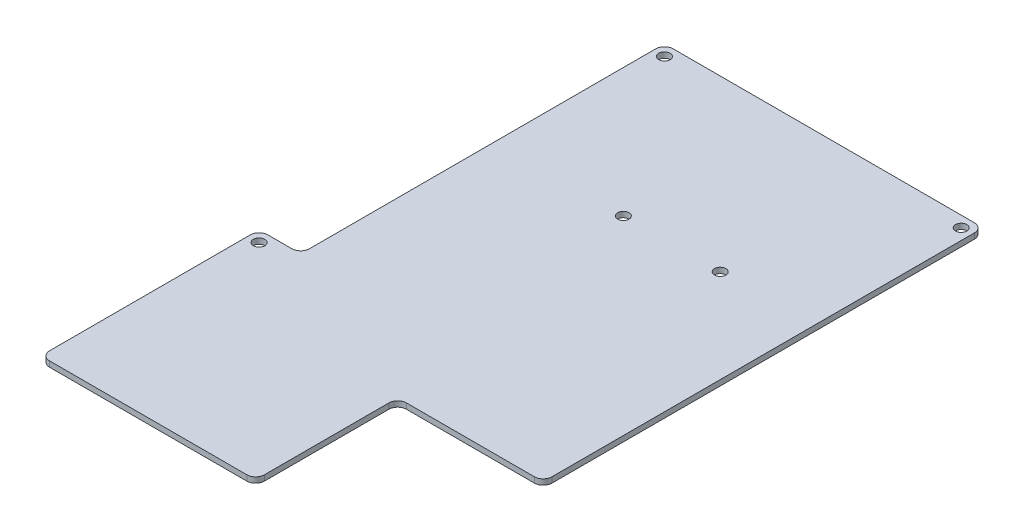
SolidWorks part; units mm, degrees
ref_plane "Front" through (0, 0, 0) normal (0, 0, 1) x (1, 0, 0)
ref_plane "Top" through (0, 0, 0) normal (0, 1, 0) x (1, 0, 0)
ref_plane "Right" through (0, 0, 0) normal (1, 0, 0) x (0, 0, -1)
sketch "Sketch1" plane through (0, 0, 0) normal (0, 1, 0) x (1, 0, 0)
  line L1 (-46, -63.5) -> (46, -63.5)
  line L2 (-46, -63.5) -> (-46, 63.5)
  line L3 (-46, 63.5) -> (46, 63.5)
  line L4 (46, -63.5) -> (46, 63.5)
  line L5 (-46, -63.5) -> (46, 63.5) construction
  line L6 (-46, 63.5) -> (46, -63.5) construction
  point P0 (0, 0)
  dimension "D1" = 127
  dimension "D2" = 92
extrude "Boss-Extrude1" add sketch "Sketch1" along normal blind 1.6
hole_wizard "#4 Clearance Hole1" positions "Sketch4" profile "Sketch5" hole size "#4" standard "ANSI Inch"
sketch "Sketch4" plane through (0, 1.6, 0) normal (0, 1, 0) x (1, 0, 0)
  line L1 (46, -63.5) -> (46, 63.5) construction
  line L2 (46, 63.5) -> (-46, 63.5) construction
  line L3 (-46, 63.5) -> (-46, -63.5) construction
  point P22 (19.05, 14.54)
  point P24 (-8.89, 14.54)
  dimension "D1" = 26.95
  dimension "D2" = 48.96
  dimension "D3" = 48.96
  dimension "D4" = 37.11
sketch "Sketch5" plane through (19.05, 1.6, -14.54) normal (1, 0, 0) x (0, 0, 1)
  line L0 (0, 0) -> (0, 19.7306)
  line L1 (0, 19.7306) -> (1.6319, 18.75)
  line L2 (1.6319, 18.75) -> (1.6319, 0)
  line L5 (1.6319, 0) -> (0, 0)
  line L10 (0, 19.7306) -> (-1.632, 18.75) construction
  line L11 (0, -6.35) -> (0, 107.95) construction
  dimension "Hole Dia." = 3.2639
  dimension "Hole Depth" = 18.75
  dimension "Drill Angle" = 118
hole_wizard "#8 Clearance Hole1" positions "Sketch6" profile "Sketch7" hole size "#8" standard "ANSI Inch"
sketch "Sketch6" plane through (0, 0, 0) normal (0, -1, 0) x (-1, 0, 0)
  circle A0 centre (22.07, -45.25) radius 1.5 construction
  point P0 (22.07, -45.25)
sketch "Sketch7" plane through (-22.07, 0, 45.25) normal (1, 0, 0) x (0, 0, -1)
  line L0 (0, 0) -> (0, 20.1007)
  line L1 (0, 20.1007) -> (2.2479, 18.75)
  line L2 (2.2479, 18.75) -> (2.2479, 0)
  line L5 (2.2479, 0) -> (0, 0)
  line L10 (0, 20.1007) -> (-2.2479, 18.75) construction
  line L11 (0, -6.35) -> (0, 107.95) construction
  dimension "Hole Dia." = 4.4958
  dimension "Hole Depth" = 18.75
  dimension "Drill Angle" = 118
sketch "Sketch8" plane through (0, 0, 0) normal (0, 1, 0) x (1, 0, 0)
  line L0 (-46, -63.5) -> (46, -63.5) construction
  line L1 (4, -41.5) -> (-58, -41.5)
  line L2 (4, -41.5) -> (4, -104.5)
  line L3 (4, -104.5) -> (-58, -104.5)
  line L4 (-58, -41.5) -> (-58, -104.5)
  line L5 (4, -41.5) -> (-58, -104.5) construction
  line L6 (4, -104.5) -> (-58, -41.5) construction
  line L7 (-46, 63.5) -> (-46, -63.5) construction
  point P0 (-27, -73)
  point P5 (-57.7847, -41.7081)
  point P6 (11.171, -104.6302)
  point P7 (2.5795, -104.8057)
  dimension "D1" = 22
  dimension "D2" = 50
  dimension "D3" = 62
  dimension "D4" = 63
extrude "Boss-Extrude2" add sketch "Sketch8" along normal blind 1.6
hole_wizard "#4 Clearance Hole2" positions "Sketch2" profile "Sketch3" hole size "#4" standard "ANSI Inch"
sketch "Sketch2" plane through (0, 1.6, 0) normal (0, 1, 0) x (1, 0, 0)
  line L1 (-42.825, 60.325) -> (42.825, 60.325)
  line L2 (-42.825, 60.325) -> (-42.825, -60.325)
  line L3 (-42.825, -60.325) -> (42.825, -60.325)
  line L4 (42.825, 60.325) -> (42.825, -60.325)
  line L5 (-42.825, 60.325) -> (42.825, -60.325) construction
  line L6 (-42.825, -60.325) -> (42.825, 60.325) construction
  line L9 (46, -63.5) -> (46, 63.5) construction
  line L10 (4, -63.5) -> (46, -63.5) construction
  line L11 (-46, -41.5) -> (-58, -41.5) construction
  line L12 (-58, -41.5) -> (-58, -104.5) construction
  point P0 (-42.825, 60.325)
  point P2 (42.825, 60.325)
  point P118 (-54.82, -44.68)
  dimension "D1" = 3.175
  dimension "D2" = 3.175
  dimension "D3" = 3.18
  dimension "D4" = 3.18
sketch "Sketch3" plane through (-42.825, 1.6, -60.325) normal (1, 0, 0) x (0, 0, 1)
  line L0 (0, 0) -> (0, 50.9806)
  line L1 (0, 50.9806) -> (1.6319, 50)
  line L2 (1.6319, 50) -> (1.6319, 0)
  line L5 (1.6319, 0) -> (0, 0)
  line L10 (0, 50.9806) -> (-1.632, 50) construction
  line L11 (0, -6.35) -> (0, 107.95) construction
  dimension "Hole Dia." = 3.2639
  dimension "Hole Depth" = 50
  dimension "Drill Angle" = 118
fillet "Fillet1" radius 2.54 8 edges at (46, 0.8, 63.5) (46, 0.8, -63.5) (-46, 0.8, -63.5) (4, 0.8, 63.5) (4, 0.8, 104.5) (-58, 0.8, 104.5) (-58, 0.8, 41.5) (-46, 0.8, 41.5)
ref_point "PCB_ORIGIN"
sketch "TOP_KEEPOUT" plane through (0, 1.6, 0) normal (0, 1, 0) x (1, 0, 0)
  circle A0 centre (-8.89, 14.54) radius 3.429
  circle A1 centre (19.05, 14.54) radius 3.429
  circle A2 centre (42.825, 60.325) radius 3.429
  circle A3 centre (-42.825, 60.325) radius 3.429
  circle A6 centre (-54.82, -44.68) radius 3.429
  dimension "D1" = 6.858
sketch "BOTTOM_KEEPOUT" plane through (0, 0, 0) normal (0, -1, 0) x (1, 0, 0)
  line L0 (-26.67, -46.036) -> (-26.67, -3.11) construction
  line L1 (26.67, -47.56) -> (-26.67, -47.56)
  line L2 (26.67, -47.56) -> (26.67, 51.5)
  line L3 (26.67, 51.5) -> (-21.67, 51.5)
  line L4 (-26.67, -47.56) -> (-26.67, 41.5)
  line L7 (-13.716, -47.56) -> (-25.146, -47.56) construction
  line L9 (26.67, -3.11) -> (26.67, -46.56) construction
  line L10 (-25.67, 51.5) -> (25.67, 51.5) construction
  line L11 (-21.67, 51.5) -> (-21.67, 41.5)
  line L12 (-21.67, 41.5) -> (-26.67, 41.5)
  circle A2 centre (42.825, -60.325) radius 3.937
  circle A3 centre (-42.825, -60.325) radius 3.937
  circle A4 centre (-54.82, 44.68) radius 3.937
  dimension "D1" = 7.874
  dimension "D4" = 5
  dimension "D5" = 10
sketch "TOP_CONN_POS" plane through (0, 1.6, 0) normal (0, 1, 0) x (1, 0, 0)
  line L0 (6.35, -35.308) -> (6.35, -45.308)
  line L1 (-37.936, 28.7076) -> (-37.936, 18.7076)
  line L2 (1.35, -40.308) -> (11.35, -40.308)
  line L3 (-42.936, 23.7076) -> (-32.936, 23.7076)
  line L4 (0, 60.436) -> (0, 50.436)
  line L5 (-5, 55.436) -> (5, 55.436)
  line L6 (-37.936, -5.35) -> (-37.936, 52.7652) construction
  line L7 (-43.524, 23.7076) -> (-32.348, 23.7076) construction
  line L8 (0, 61.024) -> (0, 49.848) construction
  line L9 (-29.0576, 55.436) -> (29.0576, 55.436) construction
  line L10 (37.936, 28.7076) -> (37.936, 18.7076)
  line L11 (32.936, 23.7076) -> (42.936, 23.7076)
  line L12 (43.524, 23.7076) -> (32.348, 23.7076) construction
  line L13 (37.936, 52.7652) -> (37.936, -5.35) construction
  line L14 (37.936, -25.0576) -> (37.936, -35.0576)
  line L15 (32.936, -30.0576) -> (42.936, -30.0576)
  line L16 (37.936, -52.7652) -> (37.936, -7.35) construction
  line L17 (43.524, -30.0576) -> (32.348, -30.0576) construction
  line L18 (0, -50.436) -> (0, -60.436)
  line L19 (-5, -55.436) -> (5, -55.436)
  line L20 (29.0576, -55.436) -> (-29.0576, -55.436) construction
  line L21 (0, -61.024) -> (0, -49.848) construction
  line L22 (6.35, -45.896) -> (6.35, -34.72) construction
  line L23 (-16.3576, -40.308) -> (29.0576, -40.308) construction
  line L24 (-41.4, -10.83) -> (-41.4, -20.83)
  line L25 (-46.4, -15.83) -> (-36.4, -15.83)
  line L26 (-41.4, -36.98) -> (-41.4, -26.98)
  line L27 (-46.4, -31.98) -> (-36.4, -31.98)
  line L28 (-0.6, -90.425) -> (-0.6, -100.425)
  line L29 (-5.6, -95.425) -> (4.4, -95.425)
  line L30 (4, -95.425) -> (-11.4, -95.425) construction
  line L31 (-0.6, -100.75) -> (-0.6, -90.1) construction
  line L32 (-41.4, -25.155) -> (-41.4, -38.805) construction
  line L33 (-46, -31.98) -> (-30.92, -31.98) construction
  line L34 (-46, -15.83) -> (-30.92, -15.83) construction
  line L35 (-41.4, -9.005) -> (-41.4, -22.655) construction
  point P2 (6.35, -40.308)
  point P9 (-37.936, 23.7076)
  point P14 (0, 55.436)
  point P17 (-41.4, -15.83)
  point P29 (37.936, 23.7076)
  point P40 (37.936, -30.0576)
  point P50 (0, -55.436)
  point P53 (-41.4, -31.98)
  point P66 (-0.6, -95.425)
  dimension "D1" = 10
  dimension "D2" = 0
  dimension "D3" = 0
  dimension "D4" = 0
  dimension "D5" = 0
  dimension "D6" = 0
  dimension "D7" = 0
  dimension "D8" = 0
  dimension "D9" = 0
  dimension "D10" = 0
  dimension "D11" = 0
  dimension "D12" = 0
  dimension "D13" = 0
  dimension "D14" = 0
  dimension "D15" = 0
  dimension "D16" = 0
  dimension "D17" = 0
  dimension "D18" = 0
  dimension "D19" = 0
sketch "BOTTOM_CONN_POS" plane through (0, 1.6, 0) normal (0, 1, 0) x (1, 0, 0)
  line L0 (0, 12.768) -> (0, -17.232)
  line L1 (-15, -2.232) -> (15, -2.232)
  line L2 (-41.4, 47.27) -> (-41.4, 37.27)
  line L3 (-46.4, 42.27) -> (-36.4, 42.27)
  line L4 (-46, 42.27) -> (-30.6, 42.27) construction
  line L5 (-41.4, 50.595) -> (-41.4, 33.945) construction
  line L6 (-41.4, 28.62) -> (-41.4, 18.62)
  line L7 (-46.4, 23.62) -> (-36.4, 23.62)
  line L8 (-41.4, 12.97) -> (-41.4, 2.97)
  line L9 (-46.4, 7.97) -> (-36.4, 7.97)
  line L10 (-41.4, 0.32) -> (-41.4, -9.68)
  line L11 (-46.4, -4.68) -> (-36.4, -4.68)
  line L12 (-41.4, -12.33) -> (-41.4, -22.33)
  line L13 (-46.4, -17.33) -> (-36.4, -17.33)
  line L14 (-46, 23.62) -> (-30.6, 23.62) construction
  line L15 (-46, 7.97) -> (-30.6, 7.97) construction
  line L16 (-46, -4.68) -> (-30.6, -4.68) construction
  line L17 (-46, -17.33) -> (-30.6, -17.33) construction
  line L18 (-39, -24.955) -> (-39, -34.955)
  line L19 (-44, -29.955) -> (-34, -29.955)
  line L20 (-41.4, -10.83) -> (-41.4, -20.83)
  line L21 (-46.4, -15.83) -> (-36.4, -15.83)
  line L32 (-39, -34.655) -> (-39, -25.255) construction
  line L33 (-42.65, -29.955) -> (-35.5, -29.955) construction
  line L34 (-46, -15.83) -> (-30.92, -15.83) construction
  line L35 (-41.4, -9.005) -> (-41.4, -22.655) construction
  line L40 (39.35, -41.555) -> (39.35, -51.555)
  line L41 (34.35, -46.555) -> (44.35, -46.555)
  line L42 (41.4, -9.33) -> (41.4, -19.33)
  line L43 (36.4, -14.33) -> (46.4, -14.33)
  line L44 (39.35, -24.455) -> (39.35, -34.455)
  line L45 (34.35, -29.455) -> (44.35, -29.455)
  line L46 (39.35, -39.355) -> (39.35, -53.755) construction
  line L47 (35.85, -46.555) -> (43, -46.555) construction
  line L48 (35.85, -29.455) -> (43, -29.455) construction
  line L49 (41.4, -9.005) -> (41.4, -19.655) construction
  line L50 (46, -14.33) -> (30.6, -14.33) construction
  line L51 (41.4, 3.32) -> (41.4, -6.68)
  line L52 (36.4, -1.68) -> (46.4, -1.68)
  line L53 (41.4, 17.47) -> (41.4, 7.47)
  line L54 (36.4, 12.47) -> (46.4, 12.47)
  line L61 (46, -1.68) -> (30.6, -1.68) construction
  line L62 (46, 12.47) -> (30.92, 12.47) construction
  line L63 (41.4, 33.12) -> (41.4, 23.12)
  line L64 (36.4, 28.12) -> (46.4, 28.12)
  line L65 (46, 28.12) -> (30.92, 28.12) construction
  line L66 (41.4, 48.77) -> (41.4, 38.77)
  line L67 (36.4, 43.77) -> (46.4, 43.77)
  line L68 (46, 43.77) -> (30.92, 43.77) construction
  line L69 (27.975, 63.9) -> (27.975, 53.9)
  line L70 (22.975, 58.9) -> (32.975, 58.9)
  line L71 (21.15, 58.9) -> (34.8, 58.9) construction
  line L72 (27.975, 63.5) -> (27.975, 48.42) construction
  line L73 (10.825, 63.9) -> (10.825, 53.9)
  line L74 (5.825, 58.9) -> (15.825, 58.9)
  line L75 (10.825, 63.5) -> (10.825, 48.1) construction
  line L76 (-7.825, 63.9) -> (-7.825, 53.9)
  line L77 (-12.825, 58.9) -> (-2.825, 58.9)
  line L78 (-7.825, 63.5) -> (-7.825, 48.1) construction
  line L79 (-26.475, 63.9) -> (-26.475, 53.9)
  line L80 (-31.475, 58.9) -> (-21.475, 58.9)
  line L81 (-26.475, 63.5) -> (-26.475, 48.1) construction
  line L82 (0, -51.5) -> (0, 50.1) construction
  line L83 (26.67, -2.232) -> (-26.67, -2.232) construction
  point P4 (0, -2.232)
  point P5 (0, 0)
  point P6 (0, 0)
  point P7 (0, 0)
  point P13 (-41.4, 42.27)
  point P24 (-41.4, 23.62)
  point P29 (-41.4, 7.97)
  point P34 (-41.4, -4.68)
  point P39 (-41.4, -17.33)
  point P56 (-39, -29.955)
  point P62 (-41.4, -15.83)
  point P105 (39.35, -46.555)
  point P110 (41.4, -14.33)
  point P115 (39.35, -29.455)
  point P135 (41.4, -1.68)
  point P140 (41.4, 12.47)
  point P151 (41.4, 28.12)
  point P161 (41.4, 43.77)
  point P169 (27.975, 58.9)
  point P179 (10.825, 58.9)
  point P188 (-7.825, 58.9)
  point P197 (-26.475, 58.9)
  dimension "D1" = 30
  dimension "D2" = 10
  dimension "D3" = 0
  dimension "D4" = 0
  dimension "D5" = 10
  dimension "D6" = 10
  dimension "D7" = 10
  dimension "D8" = 10
  dimension "D9" = 0
  dimension "D10" = 0
  dimension "D11" = 0
  dimension "D12" = 0
  dimension "D13" = 10
  dimension "D14" = 10
  dimension "D16" = 0
  dimension "D17" = 0
  dimension "D18" = 0
  dimension "D19" = 0
  dimension "D24" = 0
  dimension "D25" = 0
  dimension "D26" = 0
  dimension "D27" = 0
  dimension "D28" = 0
  dimension "D29" = 10
  dimension "D30" = 10
  dimension "D31" = 0
  dimension "D32" = 0
  dimension "D33" = 10
  dimension "D34" = 0
  dimension "D35" = 10
  dimension "D36" = 0
  dimension "D37" = 10
  dimension "D38" = 0
  dimension "D39" = 0
  dimension "D40" = 10
  dimension "D41" = 0
  dimension "D42" = 10
  dimension "D43" = 0
  dimension "D44" = 10
  dimension "D45" = 0
  dimension "D46" = 0
  dimension "D47" = 0
